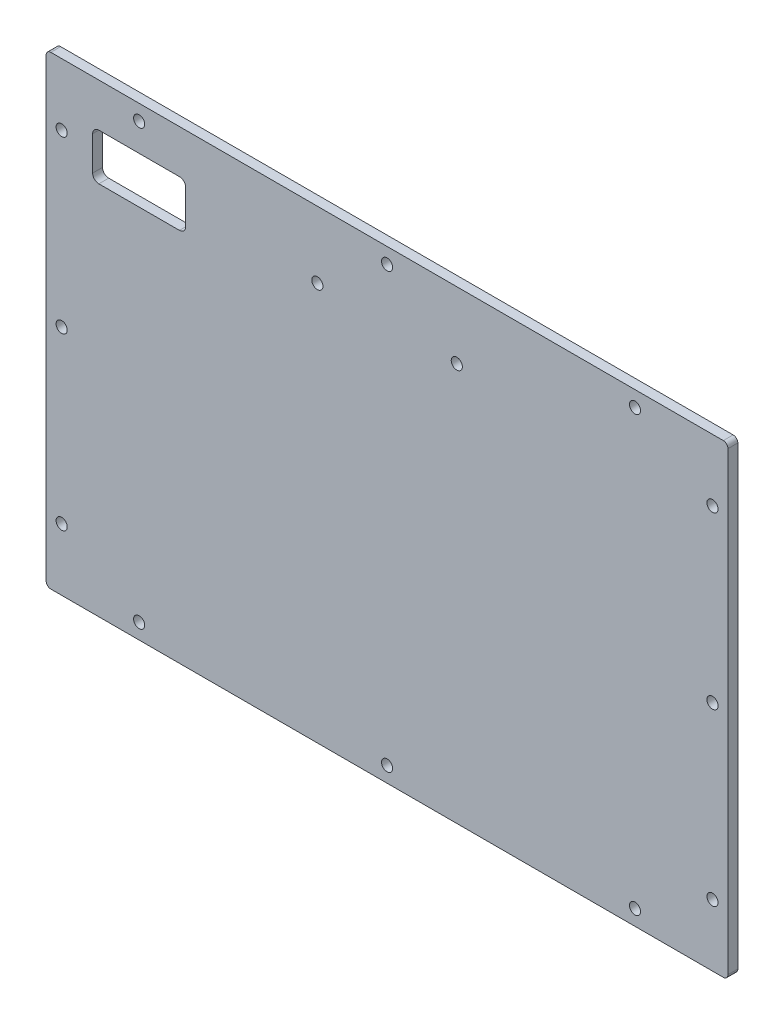
SolidWorks part; units mm, degrees
ref_plane "Front Plane" through (0, 0, 0) normal (0, 0, 1) x (1, 0, 0)
ref_plane "Top Plane" through (0, 0, 0) normal (0, 1, 0) x (1, 0, 0)
ref_plane "Right Plane" through (0, 0, 0) normal (1, 0, 0) x (0, 0, -1)
sketch "Sketch1" plane through (0, 0, 0) normal (0, 0, 1) x (1, 0, 0)
  line L0 (0, 0) -> (0, 75) construction
  line L1 (-110, -75) -> (110, -75)
  line L2 (-110, -75) -> (-110, 75)
  line L3 (-110, 75) -> (110, 75)
  line L4 (110, -75) -> (110, 75)
  line L5 (-110, -75) -> (110, 75) construction
  line L6 (-110, 75) -> (110, -75) construction
  line L15 (0, 0) -> (-110, 0) construction
  point P0 (0, 0)
  dimension "D1" = 220
  dimension "D2" = 150
extrude "Boss-Extrude1" add sketch "Sketch1" along normal blind 3.175 contours L3 L2 L1 L4 region at (0, 0, 0)
hole_wizard "M3 Clearance Hole1" positions "Sketch2" profile "Sketch3" hole size "M3" standard "ANSI Metric" end condition through all
sketch "Sketch2" plane through (0, 0, 3.175) normal (0, 0, 1) x (1, 0, 0)
  line L1 (-105, -70) -> (105, -70)
  line L2 (-105, -70) -> (-105, 70)
  line L3 (-105, 70) -> (105, 70)
  line L4 (105, -70) -> (105, 70)
  line L5 (-105, -70) -> (105, 70) construction
  line L6 (-105, 70) -> (105, -70) construction
  line L7 (-110, -75) -> (-110, 75) construction
  line L8 (-110, 75) -> (110, 75) construction
  point P2 (0, 0)
  point P113 (-80, 70)
  point P115 (80, 70)
  point P116 (0, 70)
  point P118 (-105, 55)
  point P120 (-105, 0)
  point P122 (-105, -55)
  point P124 (-80, -70)
  point P126 (0, -70)
  point P128 (80, -70)
  point P130 (105, -55)
  point P132 (105, 0)
  point P134 (105, 55)
  dimension "D1" = 5
  dimension "D2" = 5
  dimension "D3" = 80
  dimension "D4" = 80
  dimension "D5" = 55
  dimension "D6" = 55
sketch "Sketch3" plane through (0, 0, 3.175) normal (1, 0, 0) x (0, -1, 0)
  line L0 (0, 0) -> (0, 3.175)
  line L1 (0, 3.175) -> (1.8, 3.175)
  line L2 (1.8, 3.175) -> (1.8, 0)
  line L5 (1.8, 0) -> (0, 0)
  line L11 (0, -6.35) -> (0, 107.95) construction
  dimension "Thru Hole Dia." = 3.6
  dimension "Thru Hole Depth" = 3.175
sketch "Sketch4" plane through (0, 0, 3.175) normal (0, 0, 1) x (1, 0, 0)
  line L1 (-5, -5) -> (5, -5)
  line L2 (-5, -5) -> (-5, 5)
  line L3 (-5, 5) -> (5, 5)
  line L4 (5, -5) -> (5, 5)
  line L5 (-5, -5) -> (5, 5) construction
  line L6 (-5, 5) -> (5, -5) construction
  point P0 (0, 0)
  dimension "D1" = 10
  dimension "D2" = 10
extrude "Boss-Extrude2" add sketch "Sketch4" against normal through all
fillet "Fillet2" radius 1.5 4 edges at (-110, -75, 1.5875) (110, -75, 1.5875) (110, 75, 1.5875) (-110, 75, 1.5875)
sketch "Sketch7" plane through (0, 0, 3.175) normal (0, 0, 1) x (1, 0, 0)
  line L8 (-100, -65) -> (100, -65)
  line L9 (-100, 65) -> (-100, -65)
  line L10 (100, 65) -> (-100, 65)
  line L11 (100, -65) -> (100, 65)
  line L12 (-100, -65) -> (100, -65) construction
  line L13 (-100, 65) -> (-100, -65) construction
  line L14 (100, 65) -> (-100, 65) construction
  line L15 (100, -65) -> (100, 65) construction
  line L20 (-22.5, 53.5) -> (22.5, 53.5) construction
  line L22 (-49.5, 42) -> (49.5, 42) construction
  line L23 (-49.5, 42) -> (-49.5, 65) construction
  line L24 (-49.5, 65) -> (49.5, 65) construction
  line L25 (49.5, 42) -> (49.5, 65) construction
  line L26 (-49.5, 42) -> (49.5, 65) construction
  line L27 (-49.5, 65) -> (49.5, 42) construction
  line L29 (-95, 46) -> (-65, 46)
  line L30 (-95, 46) -> (-95, 61)
  line L31 (-95, 61) -> (-65, 61)
  line L32 (-65, 46) -> (-65, 61)
  line L33 (-95, 46) -> (-65, 61) construction
  line L34 (-95, 61) -> (-65, 46) construction
  point P1 (0, 65)
  point P66 (-22.5, 53.5)
  point P67 (22.5, 53.5)
  point P76 (0, 53.5)
  point P138 (-80, 53.5)
  dimension "D2" = 45
  dimension "D3" = 99
  dimension "D4" = 23
  dimension "D5" = 15
  dimension "D6" = 30
  dimension "D7" = 5
  dimension "D1" = 10
extrude "Cut-Extrude2" cut sketch "Sketch7" against normal through all
hole_wizard "M3 Clearance Hole3" positions "Sketch8" profile "Sketch9" hole size "M3" standard "ANSI Metric" end condition through all
sketch "Sketch8" plane through (0, 0, 3.175) normal (0, 0, 1) x (1, 0, 0)
  point P0 (-22.5, 53.5)
  point P3 (22.5, 53.5)
sketch "Sketch9" plane through (-22.5, 53.5, 3.175) normal (1, 0, 0) x (0, -1, 0)
  line L0 (0, 0) -> (0, 3.175)
  line L1 (0, 3.175) -> (1.8, 3.175)
  line L2 (1.8, 3.175) -> (1.8, 0)
  line L5 (1.8, 0) -> (0, 0)
  line L11 (0, -6.35) -> (0, 107.95) construction
  dimension "Thru Hole Dia." = 3.6
  dimension "Thru Hole Depth" = 3.175
fillet "Fillet3" radius 2 4 edges at (-95, 61, 1.5875) (-95, 46, 1.5875) (-65, 46, 1.5875) (-65, 61, 1.5875)
